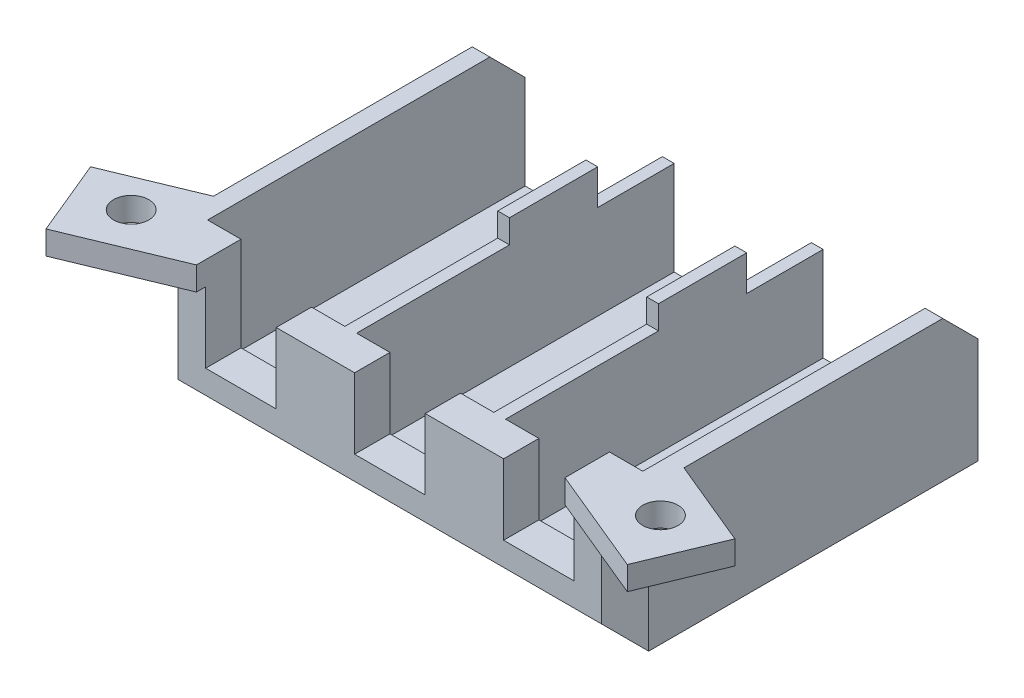
SolidWorks part; units mm, degrees
ref_plane "Front Plane" through (0, 0, 0) normal (0, 0, 1) x (1, 0, 0)
ref_plane "Top Plane" through (0, 0, 0) normal (0, 1, 0) x (1, 0, 0)
ref_plane "Right Plane" through (0, 0, 0) normal (1, 0, 0) x (0, 0, -1)
sketch "Sketch1" plane through (0, 0, 0) normal (0, 1, 0) x (1, 0, 0)
  line L1 (-20, -15) -> (20, -15)
  line L2 (-20, -15) -> (-20, 15)
  line L3 (-20, 15) -> (20, 15)
  line L4 (20, -15) -> (20, 15)
  line L5 (-20, -15) -> (20, 15) construction
  line L6 (-20, 15) -> (20, -15) construction
  point P0 (0, 0)
  dimension "D1" = 40
  dimension "D2" = 30
extrude "Boss-Extrude1" add sketch "Sketch1" along normal blind 10
sketch "Sketch5" plane through (0, 10, 0) normal (0, 1, 0) x (1, 0, 0)
  line L0 (-20, 15) -> (-20, -15) construction
  line L1 (-20, 12) -> (20, 12)
  line L2 (-20, 12) -> (-20, -15)
  line L3 (-20, -15) -> (20, -15)
  line L4 (20, 12) -> (20, -15)
  line L5 (20, 15) -> (-20, 15) construction
  dimension "D1" = 3
extrude "Boss-Extrude2" add sketch "Sketch5" along normal blind 3
sketch "Sketch2" plane through (0, 13, 0) normal (0, 1, 0) x (1, 0, 0)
  line L0 (20, 15) -> (-20, 15) construction
  line L1 (-18.5, 15) -> (-6.8333, 15)
  line L2 (-18.5, 15) -> (-18.5, -12)
  line L3 (-18.5, -12) -> (-6.8333, -12)
  line L4 (-6.8333, 15) -> (-6.8333, -12)
  line L5 (-20, 15) -> (-20, 12) construction
  line L6 (-5.8333, 15) -> (5.8333, 15)
  line L7 (-5.8333, 15) -> (-5.8333, -12)
  line L8 (-5.8333, -12) -> (5.8333, -12)
  line L9 (5.8333, 15) -> (5.8333, -12)
  line L10 (6.8333, 15) -> (18.5, 15)
  line L11 (6.8333, 15) -> (6.8333, -12)
  line L12 (6.8333, -12) -> (18.5, -12)
  line L13 (18.5, 15) -> (18.5, -12)
  line L14 (20, 12) -> (20, 15) construction
  line L15 (-20, -15) -> (20, -15) construction
  dimension "D1" = 1.5
  dimension "D2" = 1
  dimension "D3" = 1
  dimension "D4" = 1.5
  dimension "D5" = 3
extrude "Cut-Extrude1" cut sketch "Sketch2" against normal blind 11
sketch "Sketch4" plane through (0, 13, 0) normal (0, 1, 0) x (1, 0, 0)
  line L0 (-18.5, -12) -> (-6.8333, -12) construction
  line L1 (-15.6667, -12) -> (-9.6667, -12)
  line L2 (-15.6667, -12) -> (-15.6667, -15)
  line L3 (-15.6667, -15) -> (-9.6667, -15)
  line L4 (-9.6667, -12) -> (-9.6667, -15)
  line L5 (-20, -15) -> (20, -15) construction
  line L6 (-5.8333, -12) -> (5.8333, -12) construction
  line L7 (-3, -12) -> (3, -12)
  line L8 (-3, -12) -> (-3, -15)
  line L9 (-3, -15) -> (3, -15)
  line L10 (3, -12) -> (3, -15)
  line L16 (6.8333, -12) -> (18.5, -12) construction
  line L17 (9.6667, -12) -> (15.6667, -12)
  line L18 (9.6667, -12) -> (9.6667, -15)
  line L19 (9.6667, -15) -> (15.6667, -15)
  line L20 (15.6667, -12) -> (15.6667, -15)
  line L21 (18.5, 15) -> (6.8333, 15) construction
  line L22 (-6.8333, 15) -> (-18.5, 15) construction
  point P22 (12.6667, 15)
  point P23 (12.6667, -12)
  point P24 (0, -12)
  point P28 (-12.6667, 15)
  point P29 (-12.6667, -12)
  dimension "D1" = 6
extrude "Cut-Extrude2" cut sketch "Sketch4" against normal blind 8
sketch "Sketch6" plane through (0, 13, 0) normal (0, 1, 0) x (1, 0, 0)
  line L0 (9.6667, -12) -> (9.6667, -15) construction
  line L1 (-9.6667, -15) -> (9.6667, -15)
  line L2 (-9.6667, -15) -> (-9.6667, 1)
  line L3 (-9.6667, 1) -> (9.6667, 1)
  line L4 (9.6667, -15) -> (9.6667, 1)
  dimension "D1" = 16
extrude "Cut-Extrude3" cut sketch "Sketch6" against normal blind 2
chamfer "Chamfer2" distance 3 angle 45 4 edges at (19.25, 10, -12) (6.3333, 10, -12) (-6.3333, 10, -12) (-19.25, 10, -12)
sketch "Sketch8" plane through (0, 13, 0) normal (0, 1, 0) x (1, 0, 0)
  line L0 (20, -10) -> (27.391, -13.0615)
  line L1 (20, -15) -> (20, 12) construction
  line L4 (15.6667, -15) -> (20, -15) construction
  line L6 (15.6667, -15) -> (18.5, -12)
  line L7 (18.5, -12) -> (20, -10)
  line L8 (15.6667, -15) -> (15.6667, -15.7818)
  line L9 (15.6667, -15.7818) -> (24.7123, -19.5286)
  line L10 (27.391, -13.0615) -> (24.7123, -19.5286)
  line L11 (9.6667, -15) -> (15.6667, -15) construction
  dimension "D1" = 157.5
  dimension "D2" = 25
  dimension "D3" = 7
  dimension "D4" = 8
extrude "Boss-Extrude3" add sketch "Sketch8" against normal blind 2
mirror "Mirror1" about plane through (0, 0, 0) normal (1, 0, 0) of "Boss-Extrude3"
sketch "Sketch9" plane through (0, 11, 0) normal (0, -1, 0) x (1, 0, 0)
  line L0 (0, 0) -> (0, 14.5) construction
  line L1 (-22.5, 14.5) -> (22.5, 14.5) construction
  circle A0 centre (-22.5, 14.5) radius 1.5
  circle A1 centre (22.5, 14.5) radius 1.5
  point P6 (0, 14.5)
  point P7 (0, 0)
  dimension "D3" = 3
  dimension "D1" = 14.5
  dimension "D2" = 45
extrude "Cut-Extrude5" cut sketch "Sketch9" against normal up to vertex (2 mm away) up to point (18.5, 13, 12)
sketch "Sketch11" plane through (0, 0, 0) normal (0, -1, 0) x (1, 0, 0)
  line L1 (-20, 15) -> (20, 15)
  line L2 (-20, 15) -> (-20, -15)
  line L3 (-20, -15) -> (20, -15)
  line L4 (20, 15) -> (20, -15)
extrude "Cut-Extrude6" cut sketch "Sketch11" against normal blind 1
chamfer "Chamfer3" distance 2 angle 45 3 edges at (-20, 6, 15) (20, 6, 15) (0, 1, 15)
sketch "Sketch14" plane through (0, 1, 0) normal (0, -1, 0) x (1, 0, 0)
  line L0 (-20, -15) -> (20, -15) construction
  line L1 (-3, -15) -> (3, -15)
  line L2 (-3, -15) -> (-3, -13)
  line L3 (-3, -13) -> (3, -13)
  line L4 (3, -15) -> (3, -13)
  point P6 (0, -13)
  dimension "D1" = 6
  dimension "D2" = 2
extrude "Boss-Extrude4" add sketch "Sketch14" along normal blind 4
sketch "Sketch15" plane through (0, 0, -15) normal (0, 0, -1) x (-1, 0, 0)
  line L0 (-3, 1) -> (-20, 1) construction
  circle A1 centre (0, -0.5) radius 1.5
  point P3 (0, 0)
  dimension "D2" = 3
  dimension "D1" = 1.5
extrude "Cut-Extrude7" cut sketch "Sketch15" against normal blind 4
chamfer "Chamfer7" distance 4 angle 45 2 edges at (3, 1, -14) (-3, 1, -14)
sketch "Sketch16" plane through (0, 13, 0) normal (0, 1, 0) x (1, 0, 0)
  line L0 (-6.8333, -12) -> (-6.8333, 15) construction
  line L1 (-6.8333, 8.5) -> (6.8333, 8.5)
  line L2 (-6.8333, 8.5) -> (-6.8333, 15)
  line L3 (-6.8333, 15) -> (6.8333, 15)
  line L4 (6.8333, 8.5) -> (6.8333, 15)
  dimension "D1" = 6.5
extrude "Cut-Extrude8" cut sketch "Sketch16" against normal blind 3
